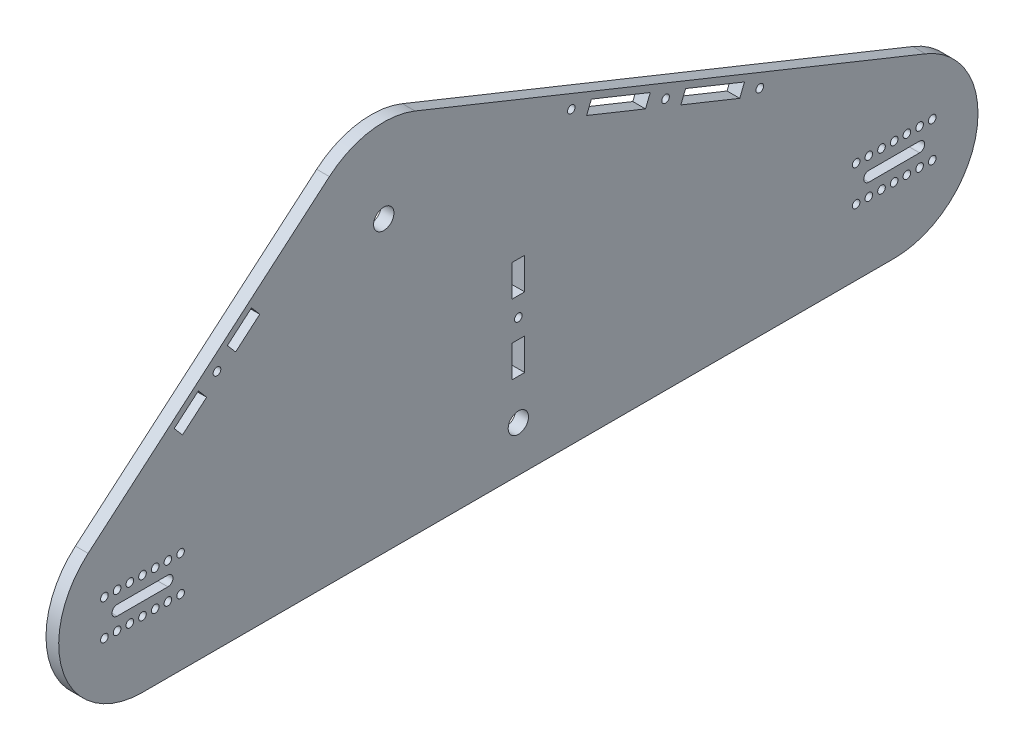
SolidWorks part; units mm, degrees
material "PMMA"
ref_plane "Piano frontale" through (0, 0, 0) normal (0, 0, 1) x (1, 0, 0)
ref_plane "Piano superiore" through (0, 0, 0) normal (0, 1, 0) x (1, 0, 0)
ref_plane "Piano destro" through (0, 0, 0) normal (1, 0, 0) x (0, 0, -1)
sketch "Schizzo5" plane through (0, 0, 0) normal (1, 0, 0) x (0, 0, -1)
  line L0 (-95, 0) -> (201, 0) construction
  line L1 (0, 81) -> (0, 0) construction
  dimension "D1" = 95
  dimension "D2" = 201
  dimension "D3" = 81
sketch "Schizzo2" plane through (0, 0, 0) normal (1, 0, 0) x (0, 0, -1)
  circle A0 centre (-95, 0) radius 2
  circle A1 centre (201, 0) radius 2
  circle A2 centre (0, 81) radius 4
  dimension "D1" = 4
  dimension "D2" = 8
sketch "Schizzo3" plane through (0, 0, 0) normal (1, 0, 0) x (0, 0, -1)
  line L0 (-95, 0) -> (-95, -14.8819) construction
  line L1 (201, 0) -> (201, -14.8819) construction
  line L2 (-95, -33) -> (201, -33)
  line L3 (-116.4107, 25.1114) -> (-21.4107, 106.1114)
  line L4 (12.3346, 111.6081) -> (213.3346, 30.6081)
  line L5 (-90.8456, 91.3374) -> (-46.9759, 39.8853) construction
  line L6 (125.4712, 102.4655) -> (100.1981, 39.7507) construction
  line L7 (53, 29.8908) -> (53, -95.8908) construction
  line L9 (184.7962, 36.718) -> (37.1353, 96.2231) construction
  arc A0 (12.3346, 111.6081) -> (-21.4107, 106.1114) centre (0, 81) ccw
  arc A1 (-116.4107, 25.1114) -> (-95, -33) centre (-95, 0) ccw
  arc A2 (213.3346, 30.6081) -> (201, -33) centre (201, 0) cw
  circle A3 centre (-95, 0) radius 47.625 construction
  circle A4 centre (201, 0) radius 47.625 construction
  circle A11 centre (-65.6667, 61.8066) radius 1.5
  circle A12 centre (110.9657, 66.4705) radius 1.5
  circle A13 centre (73.865, 81.4216) radius 1.5
  circle A14 centre (148.0665, 51.5195) radius 1.5
  point P19 (-68.9107, 65.6114)
  point P22 (112.8346, 71.1081)
  point P32 (53, -33)
  point P44 (110.9657, 66.4705)
  dimension "D2" = 33
  dimension "D3" = 95.25
  dimension "D11" = 5
  dimension "D12" = 40
  dimension "D13" = 40
  dimension "D20" = 5
extrude "Estrusione-Estrusione1" add sketch "Schizzo3" along normal blind 5
extrude "Taglio-Estrusione1" cut sketch "Schizzo2" along normal through all
sketch "Schizzo4" plane through (0, 0, 0) normal (1, 0, 0) x (0, 0, -1)
  line L5 (53, -2.6867) -> (53, -128.4682) construction
  line L11 (53, 29.8908) -> (53, -95.8908) construction
  line L24 (73.865, 81.4216) -> (110.9657, 66.4705) construction
  line L29 (80.8214, 78.6183) -> (104.0093, 69.2739) construction
  line L30 (104.9438, 71.5926) -> (103.0749, 66.9551)
  line L31 (103.0749, 66.9551) -> (79.8869, 76.2995)
  line L32 (81.7558, 80.9371) -> (79.8869, 76.2995)
  line L33 (104.9438, 71.5926) -> (81.7558, 80.9371)
  line L34 (100.1981, 39.7507) -> (119.4142, 87.4352) construction
  line L35 (125.4712, 102.4655) -> (100.1981, 39.7507) construction
  line L36 (118.8566, 65.986) -> (116.9877, 61.3484)
  line L37 (116.9877, 61.3484) -> (140.1757, 52.004)
  line L38 (142.0445, 56.6416) -> (140.1757, 52.004)
  line L39 (118.8566, 65.986) -> (142.0445, 56.6416)
  line L40 (-82.5077, 50.7328) -> (-72.9958, 58.8429)
  line L41 (-72.9958, 58.8429) -> (-69.7518, 55.0382)
  line L42 (-69.7518, 55.0382) -> (-79.2637, 46.928)
  line L43 (-79.2637, 46.928) -> (-82.5077, 50.7328)
  line L44 (-46.9759, 39.8853) -> (-90.8456, 91.3374) construction
  line L45 (-116.4107, 25.1114) -> (-21.4107, 106.1114) construction
  line L46 (-80.8857, 48.8304) -> (-50.4477, 74.7828) construction
  line L47 (-61.5816, 68.5751) -> (-58.3375, 64.7703)
  line L48 (-52.0697, 76.6852) -> (-61.5816, 68.5751)
  line L49 (-48.8257, 72.8804) -> (-52.0697, 76.6852)
  line L50 (-58.3375, 64.7703) -> (-48.8257, 72.8804)
  point P51 (92.4154, 73.9461)
  point P64 (-80.8857, 48.8304)
  point P71 (-65.6667, 61.8066)
  dimension "D14" = 25
  dimension "D15" = 5
  dimension "D16" = 12.5
  dimension "D17" = 5
  dimension "D18" = 40
extrude "Taglio-Estrusione2" cut sketch "Schizzo4" along normal through all
sketch "Schizzo6" plane through (0, 0, 0) normal (1, 0, 0) x (0, 0, -1)
  line L0 (-105, 0) -> (-85, 0) construction
  line L1 (-105, 2) -> (-85, 2)
  line L2 (-105, -2) -> (-85, -2)
  line L3 (191, 0) -> (211, 0) construction
  line L4 (191, 2) -> (211, 2)
  line L5 (191, -2) -> (211, -2)
  line L6 (-95.8595, 7) -> (49904.1405, 7) construction
  line L7 (-107.9229, 6.9974) -> (49892.0771, 6.9974) construction
  line L8 (-95, 0) -> (-95, 7) construction
  line L9 (-56.257, -7) -> (-50056.257, -7) construction
  line L10 (53, -29.7252) -> (53, 29.7252) construction
  line L11 (-95, 0) -> (201, 0) construction
  line L12 (-95, -33) -> (201, -33) construction
  line L13 (6.9793, 20.84) -> (99.0207, 20.84) construction
  line L14 (50.5, 40.84) -> (55.5, 40.84)
  line L15 (50.5, 40.84) -> (50.5, 28.34)
  line L16 (50.5, 28.34) -> (55.5, 28.34)
  line L17 (55.5, 40.84) -> (55.5, 28.34)
  line L18 (50.5, 0.84) -> (55.5, 0.84)
  line L19 (50.5, 0.84) -> (50.5, 13.34)
  line L20 (50.5, 13.34) -> (55.5, 13.34)
  line L21 (55.5, 0.84) -> (55.5, 13.34)
  line L22 (53, 28.34) -> (53, 13.34) construction
  line L23 (53, 29.8908) -> (53, -95.8908) construction
  arc A0 (-105, 2) -> (-105, -2) centre (-105, 0) ccw
  arc A1 (-85, -2) -> (-85, 2) centre (-85, 0) ccw
  arc A2 (191, 2) -> (191, -2) centre (191, 0) ccw
  arc A3 (211, -2) -> (211, 2) centre (211, 0) ccw
  circle A4 centre (-95, 7) radius 1.5
  circle A5 centre (-90, 7) radius 1.5
  circle A6 centre (-85, 7) radius 1.5
  circle A7 centre (-80, 7) radius 1.5
  circle A8 centre (53, -15) radius 4
  circle A9 centre (53, 20.84) radius 1.5
  circle A10 centre (-100, 7) radius 1.5
  circle A11 centre (-105, 7) radius 1.5
  circle A12 centre (-110, 7) radius 1.5
  circle A17 centre (-80, -7) radius 1.5
  circle A18 centre (-85, -7) radius 1.5
  circle A19 centre (-90, -7) radius 1.5
  circle A20 centre (-95, -7) radius 1.5
  circle A21 centre (-100, -7) radius 1.5
  circle A22 centre (-105, -7) radius 1.5
  circle A23 centre (-110, -7) radius 1.5
  circle A28 centre (216, -7) radius 1.5
  circle A29 centre (211, -7) radius 1.5
  circle A30 centre (206, -7) radius 1.5
  circle A31 centre (201, -7) radius 1.5
  circle A32 centre (196, -7) radius 1.5
  circle A33 centre (191, -7) radius 1.5
  circle A34 centre (186, -7) radius 1.5
  circle A39 centre (186, 7) radius 1.5
  circle A40 centre (191, 7) radius 1.5
  circle A41 centre (196, 7) radius 1.5
  circle A42 centre (201, 7) radius 1.5
  circle A43 centre (206, 7) radius 1.5
  circle A44 centre (211, 7) radius 1.5
  circle A45 centre (216, 7) radius 1.5
  point P2 (-95, 0)
  point P11 (201, 0)
  point P30 (53, 0)
  point P31 (53, 0)
  point P54 (53, 20.84)
  dimension "D2" = 2
  dimension "D4" = 2
  dimension "D7" = 3
  dimension "D10" = 8
  dimension "D13" = 3
  dimension "D1" = 10
  dimension "D3" = 10
  dimension "D5" = 7
  dimension "D6" = 7
  dimension "D11" = 18
  dimension "D12" = 5
  dimension "D14" = 12.5
  dimension "D15" = 40
  dimension "D16" = 35.84
  dimension "D8" = 4
  dimension "D9" = 4
extrude "Taglio-Estrusione4" cut sketch "Schizzo6" along direction (1, 0, 0) on the side of the normal through all
sketch "Schizzo8" plane through (0, 0, 0) normal (1, 0, 0) x (0, 0, -1)
  line L0 (0, 84) -> (0, 85) construction
  line L1 (-0.5, 84.958) -> (-0.5, 83.958)
  line L2 (0.5, 84.958) -> (0.5, 83.958)
  line L3 (3.958, 80.5) -> (2.958, 80.5)
  line L4 (3.958, 81.5) -> (2.958, 81.5)
  line L5 (-0.5, 77.042) -> (-0.5, 78.042)
  line L6 (0.5, 77.042) -> (0.5, 78.042)
  line L7 (-3.958, 81.5) -> (-2.958, 81.5)
  line L8 (-3.958, 80.5) -> (-2.958, 80.5)
  circle A0 centre (0, 81) radius 2
  circle A1 centre (0, 81) radius 3
  circle A2 centre (0, 81) radius 4 construction
  arc A3 (-0.5, 84.958) -> (0.5, 84.958) centre (0, 83.2038) cw
  arc A4 (-0.5, 83.958) -> (0.5, 83.958) centre (0, 81) cw
  arc A5 (2.958, 81.5) -> (2.958, 80.5) centre (0, 81) cw
  arc A6 (3.958, 81.5) -> (3.958, 80.5) centre (2.2038, 81) cw
  arc A7 (0.5, 78.042) -> (-0.5, 78.042) centre (0, 81) cw
  arc A8 (0.5, 77.042) -> (-0.5, 77.042) centre (0, 78.7962) cw
  arc A9 (-2.958, 80.5) -> (-2.958, 81.5) centre (0, 81) cw
  arc A10 (-3.958, 80.5) -> (-3.958, 81.5) centre (-2.2038, 81) cw
  point P33 (0, 81)
  dimension "D1" = 4
  dimension "D2" = 6
  dimension "D5" = 4
  dimension "D3" = 0.5
  dimension "D4" = 0.5
  dimension "D6" = 1
  dimension "D7" = 1
extrude "Estrusione-Estrusione2" [suppressed] add sketch "Schizzo8" along normal blind 5 contours A1 A4 A0 | L0 A1 L2 A3 | A4 L0 A3 L1 | A10 L8 A1 L7 | A8 L6 A1 L5 | A6 L4 A1 L3
equation "\"Thickness\"=5"
equation "\"D1@Estrusione-Estrusione1\"=\"Thickness\""
equation "\"D17@Schizzo4\"=\"Thickness\""
equation "\"D15@Schizzo4\"=\"Thickness\""
equation "\"D6@Schizzo6\"=\"D5@Schizzo6\""
equation "\"D1@Estrusione-Estrusione2\"=\"Thickness\""
